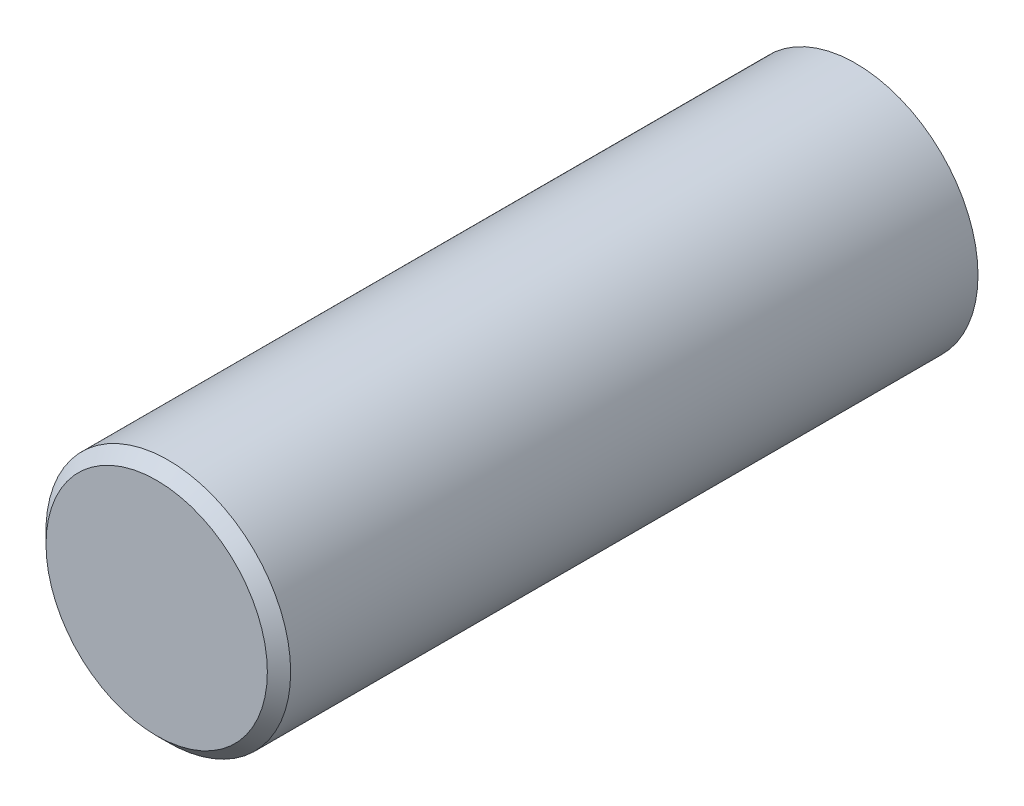
SolidWorks part; units mm, degrees
ref_plane "Front" through (0, 0, 0) normal (0, 0, 1) x (1, 0, 0)
ref_plane "Top" through (0, 0, 0) normal (0, 1, 0) x (1, 0, 0)
ref_plane "Right" through (0, 0, 0) normal (1, 0, 0) x (0, 0, -1)
sketch "Esquisse1" plane through (0, 0, 0) normal (0, 0, 1) x (1, 0, 0)
  circle A0 centre (0, 0) radius 5.25
  dimension "D1" = 10.5
extrude "Boss.-Extru.1" add sketch "Esquisse1" along normal blind 30
chamfer "Chanfrein1" distance 0.5 angle 45 1 edges at (5.25, 0, 30)
